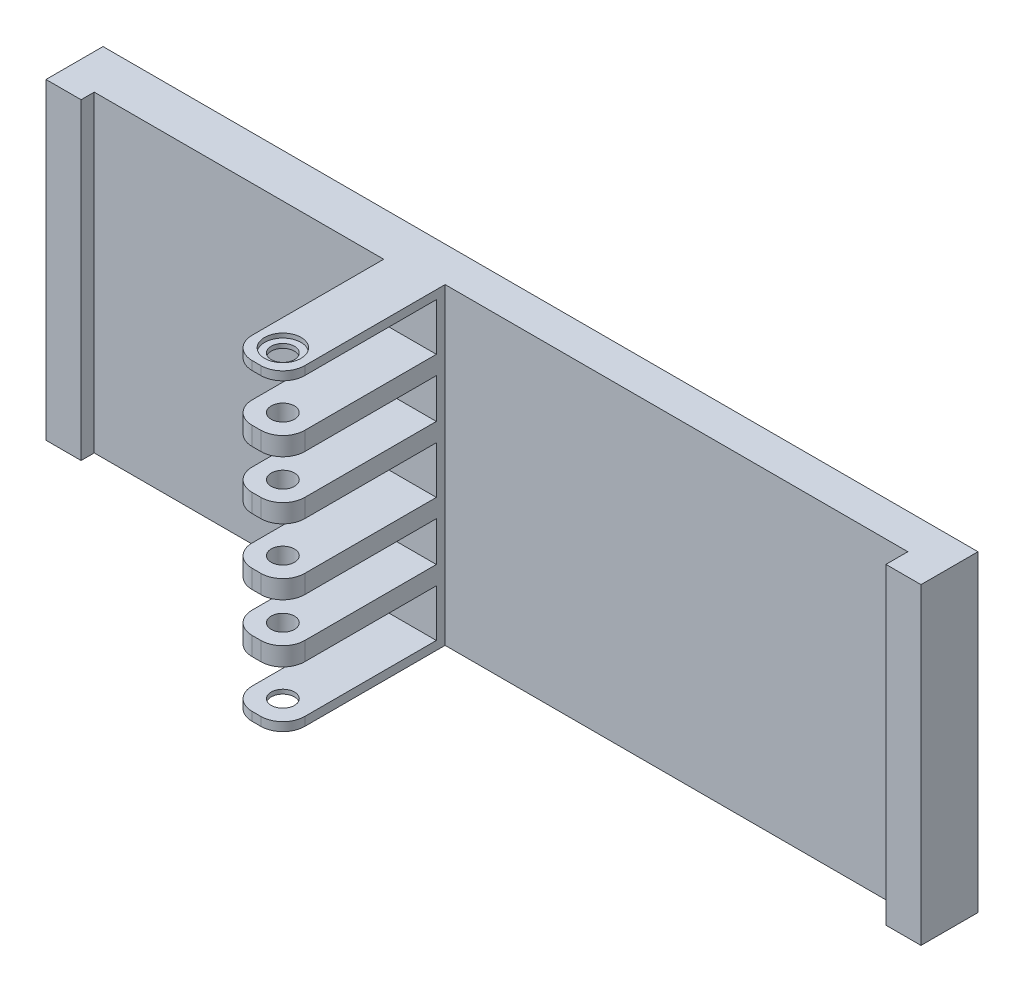
SolidWorks part; units mm, degrees
ref_plane "Front Plane" through (0, 0, 0) normal (1, 0, 0) x (0, 1, 0)
ref_plane "Top Plane" through (0, 0, 0) normal (0, 0, 1) x (0, 1, 0)
ref_plane "Right Plane" through (0, 0, 0) normal (0, 1, 0) x (-1, 0, 0)
sketch "Sketch1" plane through (0, 0, 0) normal (0, 0, 1) x (0, 1, 0)
  line L1 (0, 0) -> (-71.25, 0)
  line L2 (0, 0) -> (0, 12)
  line L3 (0, 12) -> (-71.25, 12)
  line L4 (-71.25, 0) -> (-71.25, 12)
  dimension "D1" = 71.25
  dimension "D2" = 12
extrude "Boss-Extrude1" add sketch "Sketch1" along normal blind 10 contours L3 L4 L1 L2
sketch "Sketch3" plane through (0, 0, 10) normal (0, 0, 1) x (1, 0, 0)
  line L0 (0, 0) -> (0, -71.25) construction
  line L1 (-12, 0) -> (0, 0)
  line L2 (-12, 0) -> (-12, -1.975)
  line L3 (-12, -1.975) -> (0, -1.975)
  line L4 (0, 0) -> (0, -1.975)
  line L6 (-12, -1.975) -> (0, -1.975) construction
  line L8 (-12, -12.775) -> (0, -12.775) construction
  line L10 (-12, -12.775) -> (0, -12.775)
  line L11 (-12, -12.775) -> (-12, -16.975)
  line L12 (-12, -16.975) -> (0, -16.975)
  line L13 (0, -12.775) -> (0, -16.975)
  line L14 (-12, -16.975) -> (0, -16.975) construction
  line L16 (-12, -26.025) -> (0, -26.025) construction
  line L18 (0, -26.025) -> (-12, -26.025)
  line L19 (0, -26.025) -> (0, -30.225)
  line L20 (0, -30.225) -> (-12, -30.225)
  line L21 (-12, -26.025) -> (-12, -30.225)
  line L23 (-12, -30.225) -> (0, -30.225) construction
  dimension "D1" = 1.975
  dimension "D2" = 10.8
  dimension "D3" = 4.2
  dimension "D4" = 9.05
  dimension "D5" = 4.2
extrude "Boss-Extrude2" add sketch "Sketch3" along normal blind 35
fillet "Fillet1" radius 5 6 edges at (-12, -0.9875, 45) (0, -0.9875, 45) (-12, -14.875, 45) (0, -14.875, 45) (-12, -28.125, 45) (0, -28.125, 45)
ref_plane "Plane1" through (0, -35.625, 0) normal (0, 1, 0) x (1, 0, 0)
mirror "Mirror1" about plane through (0, -35.625, 0) normal (0, 1, 0) of "Fillet1", "Boss-Extrude2"
sketch "Sketch5" plane through (0, 0, 0) normal (0, 1, 0) x (-1, 0, 0)
  line L0 (5, 45) -> (7, 45) construction
  line L1 (6, 45) -> (0, 45)
  line L2 (6, 45) -> (6, 39)
  line L3 (6, 39) -> (0, 39)
  line L4 (0, 45) -> (0, 39)
  circle A0 centre (6, 39) radius 2.65
  dimension "D1" = 6
extrude "Cut-Extrude1" cut sketch "Sketch5" against normal through all contours A0
sketch "Sketch7" plane through (0, 0, 0) normal (0, 1, 0) x (-1, 0, 0)
  line L0 (5, 45) -> (7, 45) construction
  line L1 (6, 45) -> (0, 45)
  line L2 (6, 45) -> (6, 39)
  line L3 (6, 39) -> (0, 39)
  line L4 (0, 45) -> (0, 39)
  line L5 (0, 40) -> (0, 0) construction
  circle A0 centre (6, 39) radius 4.15
  circle M6 centre (6, 39) radius 2.65
  dimension "D1" = 6
extrude "Cut-Extrude2" cut sketch "Sketch7" against normal blind 1 contours L3 A0 L2 M6 | L2 A0 L3 M6 region at (-8.8515, 0, 41.8515) region at (-3.8004, 0, 41.1996)
mirror "Mirror2" about plane through (0, -35.625, 0) normal (0, 1, 0) of "Cut-Extrude2"
sketch "Sketch8" plane through (0, 0, 0) normal (0, 0, -1) x (1, 0, 0)
  line L0 (0, 71.25) -> (-12, 71.25) construction
  line L1 (-6, 71.25) -> (-86, 71.25)
  line L2 (-6, 71.25) -> (-6, 0)
  line L3 (-6, 0) -> (-86, 0)
  line L4 (-86, 71.25) -> (-86, 0)
  line L5 (-6, 71.25) -> (113.5, 71.25)
  line L6 (-6, 71.25) -> (-6, 0)
  line L7 (-6, 0) -> (113.5, 0)
  line L8 (113.5, 71.25) -> (113.5, 0)
  line L9 (0, 0) -> (-12, 0) construction
  line M2 (0, 0) -> (0, 71.25)
  line M4 (-12, 71.25) -> (-12, 0)
  dimension "D1" = 119.5
  dimension "D2" = 80
extrude "Boss-Extrude3" add sketch "Sketch8" against normal blind 8 contours L1 L4 L3 M4 | L8 L5 L7 M2 region at (-49, -35.625, 0) region at (56.75, -35.625, 0)
sketch "Sketch9" plane through (0, 0, 8) normal (0, 0, 1) x (1, 0, 0)
  line L0 (0, -71.25) -> (113.5, -71.25) construction
  line L1 (113.5, 0) -> (105.5, 0)
  line L2 (113.5, 0) -> (113.5, -71.25)
  line L3 (113.5, -71.25) -> (105.5, -71.25)
  line L4 (105.5, 0) -> (105.5, -71.25)
  line L5 (-12, -71.25) -> (-86, -71.25) construction
  line L6 (-86, 0) -> (-78, 0)
  line L7 (-86, 0) -> (-86, -71.25)
  line L8 (-86, -71.25) -> (-78, -71.25)
  line L9 (-78, 0) -> (-78, -71.25)
  dimension "D1" = 8
extrude "Boss-Extrude4" add sketch "Sketch9" along normal blind 5
sketch "Sketch12" plane through (-12, 0, 0) normal (-1, 0, 0) x (0, -1, 0)
  line L0 (71.25, 40) -> (71.25, 8) construction
  line L1 (0, 8) -> (71.25, 8)
  line L2 (0, 8) -> (0, 10)
  line L3 (0, 10) -> (71.25, 10)
  line L4 (71.25, 8) -> (71.25, 10)
sketch "Sketch11" plane through (0, 0, 13) normal (0, 0, 1) x (1, 0, 0)
  line L0 (109.5, 0) -> (109.5, -71.25) construction
  line L1 (113.5, 0) -> (105.5, 0) construction
  line L2 (105.5, -71.25) -> (113.5, -71.25) construction
  line L3 (109.5, -10) -> (109.5, -30) construction
  line L4 (111.5, -10) -> (111.5, -30)
  line L5 (107.5, -10) -> (107.5, -30)
  line L7 (113.5, 0) -> (109.5, 0)
  line L8 (113.5, 0) -> (113.5, -10)
  line L9 (113.5, -10) -> (109.5, -10)
  line L10 (109.5, 0) -> (109.5, -10)
  arc A0 (111.5, -10) -> (107.5, -10) centre (109.5, -10) ccw
  arc A1 (107.5, -30) -> (111.5, -30) centre (109.5, -30) ccw
  point P8 (109.5, -20)
  dimension "D1" = 10
  dimension "D2" = 20
extrude "Cut-Extrude3" [suppressed] cut sketch "Sketch11" against normal blind 10 contours L4 A1 L5 A0
pattern_linear "LPattern1" [suppressed] count 2 spacing 55 of bodies 112
extrude "Boss-Extrude5" add sketch "Sketch12" along normal up to next
equation "\"whitekey_cutout_length\"= 101.5"
equation "\"mount_recess_length\"=50"
equation "\"mount_recess_height\"=12.5"
equation "\"mount_recess_depth\"=1.5"
equation "\"wall_thickness\"=8"
equation "\"D1@Sketch9\"=\"wall_thickness\""
equation "\"D2@Sketch9\"=\"wall_thickness\""
equation "\"D1@Boss-Extrude3\"=\"wall_thickness\""
equation "\"base_mount_height\"=35"
equation "\"D1@Boss-Extrude2\"=\"base_mount_height\""
equation "\"base_rear_length\"=80"
equation "\"D1@Sketch8\"=\"wall_thickness\"+110+1.5"
equation "\"D2@Sketch8\"=\"base_rear_length\""
